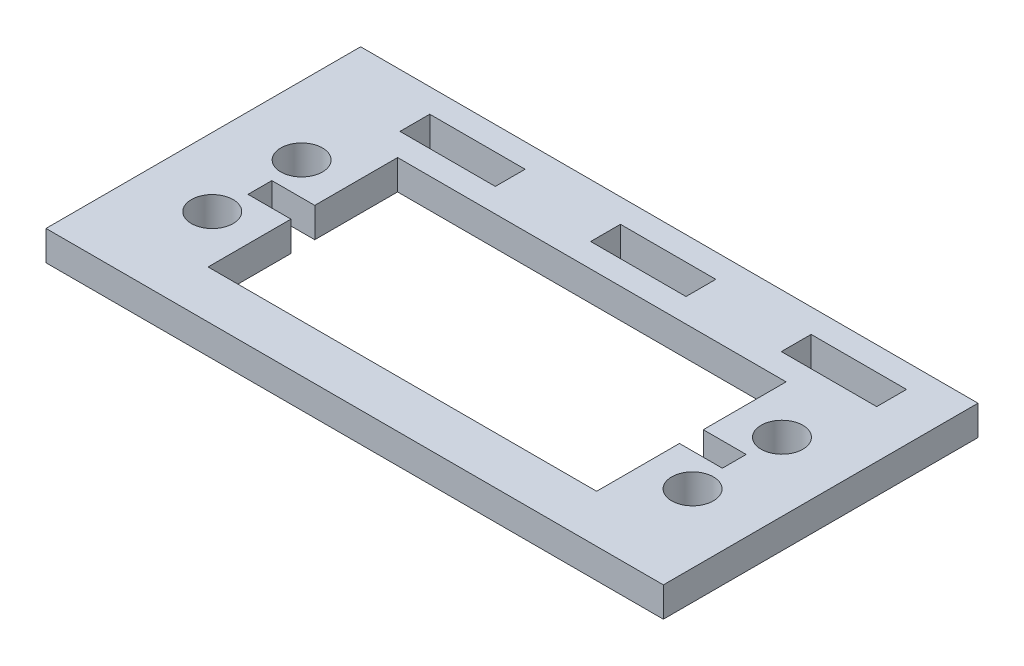
SolidWorks part; units mm, degrees
ref_plane "Front Plane" through (0, 0, 0) normal (0, 0, 1) x (1, 0, 0)
ref_plane "Top Plane" through (0, 0, 0) normal (0, 1, 0) x (1, 0, 0)
ref_plane "Right Plane" through (0, 0, 0) normal (1, 0, 0) x (0, 0, -1)
sketch "Sketch1" plane through (0, 0, 0) normal (0, 1, 0) x (1, 0, 0)
  line L0 (27.813, -10.0965) -> (32.893, -10.0965) construction
  line L1 (32.893, 18.3515) -> (-32.893, 18.3515)
  line L2 (32.893, 18.3515) -> (32.893, -15.1765)
  line L3 (32.893, -15.1765) -> (-32.893, -15.1765)
  line L4 (-32.893, 18.3515) -> (-32.893, -15.1765)
  line L5 (27.813, -10.0965) -> (27.813, -15.1765) construction
  line L6 (-27.813, -10.0965) -> (-32.893, -10.0965) construction
  line L7 (-27.813, 10.0965) -> (27.813, 10.0965) construction
  line L8 (-27.813, 10.0965) -> (-27.813, -10.0965) construction
  line L9 (-27.813, -10.0965) -> (27.813, -10.0965) construction
  line L10 (27.813, 10.0965) -> (27.813, -10.0965) construction
  line L11 (-27.813, 10.0965) -> (27.813, -10.0965) construction
  line L12 (-27.813, -10.0965) -> (27.813, 10.0965) construction
  line L13 (27.813, 15.8115) -> (27.813, 18.3515) construction
  line L14 (27.813, 15.8115) -> (17.653, 15.8115)
  line L15 (27.813, 15.8115) -> (27.813, 12.6365)
  line L16 (27.813, 12.6365) -> (17.653, 12.6365)
  line L17 (17.653, 15.8115) -> (17.653, 12.6365)
  line L18 (27.813, 15.8115) -> (17.653, 12.6365) construction
  line L19 (27.813, 12.6365) -> (17.653, 15.8115) construction
  line L20 (27.813, 12.6365) -> (27.813, 10.0965) construction
  line L21 (7.493, 15.8115) -> (7.493, 12.6365)
  line L22 (7.493, 15.8115) -> (-2.667, 15.8115)
  line L23 (7.493, 12.6365) -> (-2.667, 12.6365)
  line L24 (-2.667, 15.8115) -> (-2.667, 12.6365)
  line L25 (-12.827, 15.8115) -> (-12.827, 12.6365)
  line L26 (-12.827, 15.8115) -> (-22.987, 15.8115)
  line L27 (-12.827, 12.6365) -> (-22.987, 12.6365)
  line L28 (-22.987, 15.8115) -> (-22.987, 12.6365)
  line L29 (-20.701, 0) -> (-27.813, 0) construction
  line L30 (-20.701, -10.0965) -> (20.701, -10.0965)
  line L31 (-20.701, -10.0965) -> (-20.701, 10.0965) construction
  line L32 (-20.701, 10.0965) -> (20.701, 10.0965)
  line L33 (20.701, -10.0965) -> (20.701, 10.0965) construction
  line L34 (-20.701, -10.0965) -> (20.701, 10.0965) construction
  line L35 (-20.701, 10.0965) -> (20.701, -10.0965) construction
  line L36 (20.701, 0) -> (27.813, 0) construction
  line L37 (-27.813, 9.525) -> (27.813, 9.525) construction
  line L38 (-27.813, -9.525) -> (27.813, -9.525) construction
  line L39 (-25.5905, 9.525) -> (-25.5905, 0) construction
  line L40 (-25.5905, 0) -> (-25.5905, -9.525) construction
  line L41 (-25.5905, 4.7625) -> (25.5905, 4.7625) construction
  line L42 (-25.5905, -4.7625) -> (25.5905, -4.7625) construction
  line L43 (0, 0) -> (0, 6.8647) construction
  line L44 (20.701, 1.27) -> (25.273, 1.27)
  line L46 (20.701, -1.27) -> (25.273, -1.27)
  line L47 (25.273, 1.27) -> (25.273, -1.27)
  line L48 (-20.701, 1.27) -> (-25.273, 1.27)
  line L49 (-25.273, 1.27) -> (-25.273, -1.27)
  line L50 (-20.701, -1.27) -> (-25.273, -1.27)
  line L51 (-20.701, 10.0965) -> (-20.701, 1.27)
  line L52 (-20.701, -1.27) -> (-20.701, -10.0965)
  line L53 (20.701, -10.0965) -> (20.701, -1.27)
  line L54 (20.701, 1.27) -> (20.701, 10.0965)
  circle A0 centre (-25.5905, 4.7625) radius 2.2225
  circle A1 centre (-25.5905, -4.7625) radius 2.2225
  circle A2 centre (25.5905, 4.7625) radius 2.2225
  circle A3 centre (25.5905, -4.7625) radius 2.2225
  point P0 (0, 0)
  point P4 (22.733, 14.224)
  point P6 (0, 0)
  point P20 (0, 0)
  dimension "D9" = 4.445
  dimension "D1" = 20.193
  dimension "D2" = 55.626
  dimension "D3" = 5.08
  dimension "D4" = 3.175
  dimension "D5" = 10.16
  dimension "D6" = 2.54
  dimension "D7" = 3
  dimension "D8" = 7.112
  dimension "D10" = 19.05
  dimension "D11" = 4.572
  dimension "D12" = 2.54
extrude "Boss-Extrude2" add sketch "Sketch1" along normal blind 3.175 contours L1 L4 L3 L2 A3 A2 A1 A0 L28 L26 L25 L27 L24 L22 L21 L23 L17 L14 L15 L16 L31 L50 L49 L48 L32 L33 L44 L47 L46 L30 region at (32.1546, 0, -1.5875)
sketch "Sketch2" plane through (0, 0, 0) normal (0, 1, 0) x (1, 0, 0)
  line L30 (32.9692, -15.2527) -> (32.9692, 18.4277)
  line L31 (-32.9692, -15.2527) -> (32.9692, -15.2527)
  line L32 (-32.9692, 18.4277) -> (-32.9692, -15.2527)
  line L33 (32.9692, 18.4277) -> (-32.9692, 18.4277)
  line L34 (32.9692, -15.2527) -> (32.9692, 18.4277)
  line L35 (-32.9692, -15.2527) -> (32.9692, -15.2527)
  line L36 (-32.9692, 18.4277) -> (-32.9692, -15.2527)
  line L37 (32.9692, 18.4277) -> (-32.9692, 18.4277)
  line L48 (-12.9032, 12.7127) -> (-12.9032, 15.7353)
  line L49 (-12.9032, 15.7353) -> (-22.9108, 15.7353)
  line L50 (-22.9108, 15.7353) -> (-22.9108, 12.7127)
  line L51 (-22.9108, 12.7127) -> (-12.9032, 12.7127)
  line L52 (-12.9032, 12.7127) -> (-12.9032, 15.7353)
  line L53 (-12.9032, 15.7353) -> (-22.9108, 15.7353)
  line L54 (-22.9108, 15.7353) -> (-22.9108, 12.7127)
  line L55 (-22.9108, 12.7127) -> (-12.9032, 12.7127)
  line L60 (7.4168, 12.7127) -> (7.4168, 15.7353)
  line L61 (7.4168, 15.7353) -> (-2.5908, 15.7353)
  line L62 (-2.5908, 15.7353) -> (-2.5908, 12.7127)
  line L63 (-2.5908, 12.7127) -> (7.4168, 12.7127)
  line L64 (7.4168, 12.7127) -> (7.4168, 15.7353)
  line L65 (7.4168, 15.7353) -> (-2.5908, 15.7353)
  line L66 (-2.5908, 15.7353) -> (-2.5908, 12.7127)
  line L67 (-2.5908, 12.7127) -> (7.4168, 12.7127)
  line L72 (27.7368, 12.7127) -> (27.7368, 15.7353)
  line L73 (27.7368, 15.7353) -> (17.7292, 15.7353)
  line L74 (17.7292, 15.7353) -> (17.7292, 12.7127)
  line L75 (17.7292, 12.7127) -> (27.7368, 12.7127)
  line L76 (27.7368, 12.7127) -> (27.7368, 15.7353)
  line L77 (27.7368, 15.7353) -> (17.7292, 15.7353)
  line L78 (17.7292, 15.7353) -> (17.7292, 12.7127)
  line L79 (17.7292, 12.7127) -> (27.7368, 12.7127)
  line L128 (33.0454, -15.3289) -> (33.0454, 18.5039)
  line L129 (33.0454, 18.5039) -> (-33.0454, 18.5039)
  line L130 (-33.0454, 18.5039) -> (-33.0454, -15.3289)
  line L131 (-33.0454, -15.3289) -> (33.0454, -15.3289)
  line L167 (-20.6248, 1.1938) -> (-25.1968, 1.1938)
  line L168 (-25.1968, 1.1938) -> (-25.1968, -1.1938)
  line L169 (-25.1968, -1.1938) -> (-20.6248, -1.1938)
  line L170 (-20.6248, -1.1938) -> (-20.6248, -10.0203)
  line L171 (-20.6248, -10.0203) -> (20.6248, -10.0203)
  line L172 (20.6248, -10.0203) -> (20.6248, -1.1938)
  line L173 (20.6248, -1.1938) -> (25.1968, -1.1938)
  line L174 (25.1968, -1.1938) -> (25.1968, 1.1938)
  line L175 (25.1968, 1.1938) -> (20.6248, 1.1938)
  line L176 (20.6248, 1.1938) -> (20.6248, 10.0203)
  line L177 (20.6248, 10.0203) -> (-20.6248, 10.0203)
  line L178 (-20.6248, 10.0203) -> (-20.6248, 1.1938)
  line L179 (-20.6248, 1.1938) -> (-25.1968, 1.1938)
  line L180 (-25.1968, 1.1938) -> (-25.1968, -1.1938)
  line L181 (-25.1968, -1.1938) -> (-20.6248, -1.1938)
  line L182 (-20.6248, -1.1938) -> (-20.6248, -10.0203)
  line L183 (-20.6248, -10.0203) -> (20.6248, -10.0203)
  line L184 (20.6248, -10.0203) -> (20.6248, -1.1938)
  line L185 (20.6248, -1.1938) -> (25.1968, -1.1938)
  line L186 (25.1968, -1.1938) -> (25.1968, 1.1938)
  line L187 (25.1968, 1.1938) -> (20.6248, 1.1938)
  line L188 (20.6248, 1.1938) -> (20.6248, 10.0203)
  line L189 (20.6248, 10.0203) -> (-20.6248, 10.0203)
  line L190 (-20.6248, 10.0203) -> (-20.6248, 1.1938)
  circle A47 centre (-25.5905, 4.7625) radius 2.1463
  circle A48 centre (-25.5905, 4.7625) radius 2.1463
  circle A50 centre (-25.5905, -4.7625) radius 2.1463
  circle A51 centre (-25.5905, -4.7625) radius 2.1463
  circle A56 centre (25.5905, 4.7625) radius 2.1463
  circle A57 centre (25.5905, 4.7625) radius 2.1463
  circle A59 centre (25.5905, -4.7625) radius 2.1463
  circle A60 centre (25.5905, -4.7625) radius 2.1463
  dimension "D1" = 0.0762
  dimension "D2" = 0.0762
  dimension "D3" = 0.0762
  dimension "D4" = 0.0762
  dimension "D5" = 0.0762
  dimension "D6" = 0.0762
  dimension "D7" = 0.0762
  dimension "D8" = 0.0762
  dimension "D9" = 0.0762
  dimension "D10" = 0.0762
